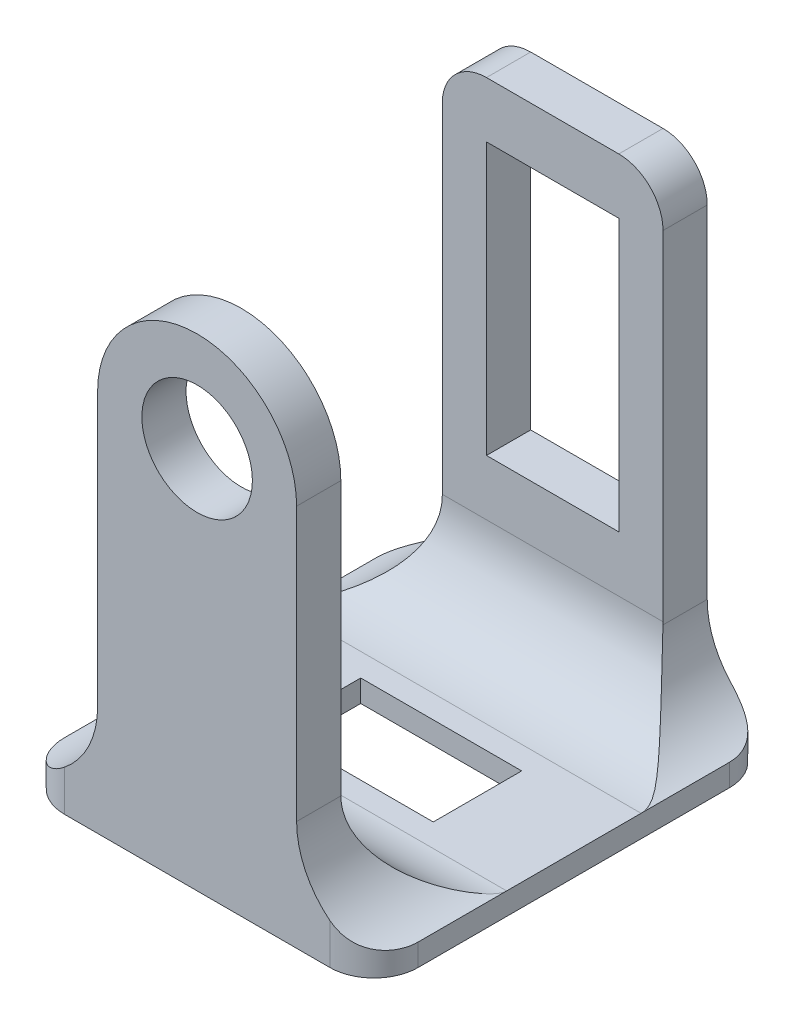
SolidWorks part; units mm, degrees
material "ABS PC"
ref_plane "Front Plane" through (0, 0, 0) normal (0, 0, 1) x (1, 0, 0)
ref_plane "Top Plane" through (0, 0, 0) normal (0, 1, 0) x (1, 0, 0)
ref_plane "Right Plane" through (0, 0, 0) normal (1, 0, 0) x (0, 0, -1)
sketch "Sketch1" plane through (0, 0, 0) normal (0, 1, 0) x (1, 0, 0)
  line L1 (-25.4, -28.702) -> (25.4, -28.702)
  line L2 (-25.4, -28.702) -> (-25.4, 28.702)
  line L3 (-25.4, 28.702) -> (25.4, 28.702)
  line L4 (25.4, -28.702) -> (25.4, 28.702)
  line L5 (-25.4, -28.702) -> (25.4, 28.702) construction
  line L6 (-25.4, 28.702) -> (25.4, -28.702) construction
  line L7 (-11.557, -6.35) -> (11.557, -6.35)
  line L8 (-11.557, -6.35) -> (-11.557, 6.35)
  line L9 (-11.557, 6.35) -> (11.557, 6.35)
  line L10 (11.557, -6.35) -> (11.557, 6.35)
  line L11 (-11.557, -6.35) -> (11.557, 6.35) construction
  line L12 (-11.557, 6.35) -> (11.557, -6.35) construction
  point P0 (0, 0)
  point P6 (0, 0)
  dimension "D1" = 57.404
  dimension "D2" = 50.8
  dimension "D3" = 12.7
  dimension "D4" = 23.114
extrude "Boss-Extrude1" add sketch "Sketch1" along normal blind 3.175
sketch "Sketch2" plane through (0, 0, -28.702) normal (0, 0, 1) x (1, 0, 0)
  line L14 (-9.5, 62.875) -> (-9.5, 23.875)
  line L15 (9.5, 62.875) -> (9.5, 23.875)
  line L22 (15.85, 15.875) -> (15.85, 3.175)
  line L39 (9.5, 62.875) -> (-9.5, 62.875)
  line L41 (15.85, 15.875) -> (15.85, 70.875)
  line L42 (15.85, 70.875) -> (-15.85, 70.875)
  line L43 (-15.85, 70.875) -> (-15.85, 15.875)
  line L45 (9.5, 23.875) -> (-9.5, 23.875)
  line L46 (15.85, 15.875) -> (-15.85, 15.875)
  line L47 (25.4, 3.175) -> (-25.4, 3.175) construction
  line L48 (15.85, 3.175) -> (-15.85, 3.175)
  line L49 (-15.85, 3.175) -> (-15.85, 15.875)
  point P1 (0, 15.875)
  point P16 (0, 47.625)
  dimension "D3" = 55
  dimension "D1" = 19
  dimension "D2" = 39
  dimension "D4" = 6.35
  dimension "D7" = 12.7
  dimension "D5" = 6.35
  dimension "D6" = 8
extrude "Boss-Extrude2" add sketch "Sketch2" along normal blind 6.35 from surface at 0
sketch "Sketch12" plane through (0, 0, 28.702) normal (0, 0, 1) x (1, 0, 0)
  line L0 (-14.2875, 54.991) -> (-14.2875, 3.175)
  line L1 (9.5, 23.875) -> (9.5, 62.875) construction
  line L2 (14.2875, 54.991) -> (14.2875, 3.175)
  line L3 (-9.5, 23.875) -> (-9.5, 62.875) construction
  line L4 (0, 3.175) -> (0, 54.991) construction
  line L5 (-25.4, 3.175) -> (25.4, 3.175) construction
  line L6 (-14.2875, 3.175) -> (14.2875, 3.175)
  arc A0 (14.2875, 54.991) -> (-14.2875, 54.991) centre (0, 54.991) ccw
  circle A1 centre (0, 54.991) radius 7.9375
  dimension "D3" = 28.575
  dimension "D4" = 15.875
  dimension "D2" = 19
  dimension "D1" = 51.816
extrude "Boss-Extrude11" add sketch "Sketch12" against normal blind 6.35
fillet "Fillet2" radius 12.7 2 edges at (-15.85, 3.175, -25.527) (15.85, 3.175, -25.527)
fillet "Fillet3" radius 12.7 1 edges at (0, 3.175, -22.352)
fillet "Fillet4" radius 12.7 2 edges at (14.2875, 3.175, 25.527) (-14.2875, 3.175, 25.527)
fillet "Fillet5" radius 12.7 1 edges at (0, 3.175, 22.352)
fillet "Fillet1" radius 6.35 6 edges at (-25.4, 1.5875, -28.702) (25.4, 1.5875, -28.702) (-25.4, 1.5875, 28.702) (25.4, 1.5875, 28.702) (-15.85, 70.875, -25.527) (15.85, 70.875, -25.527)
